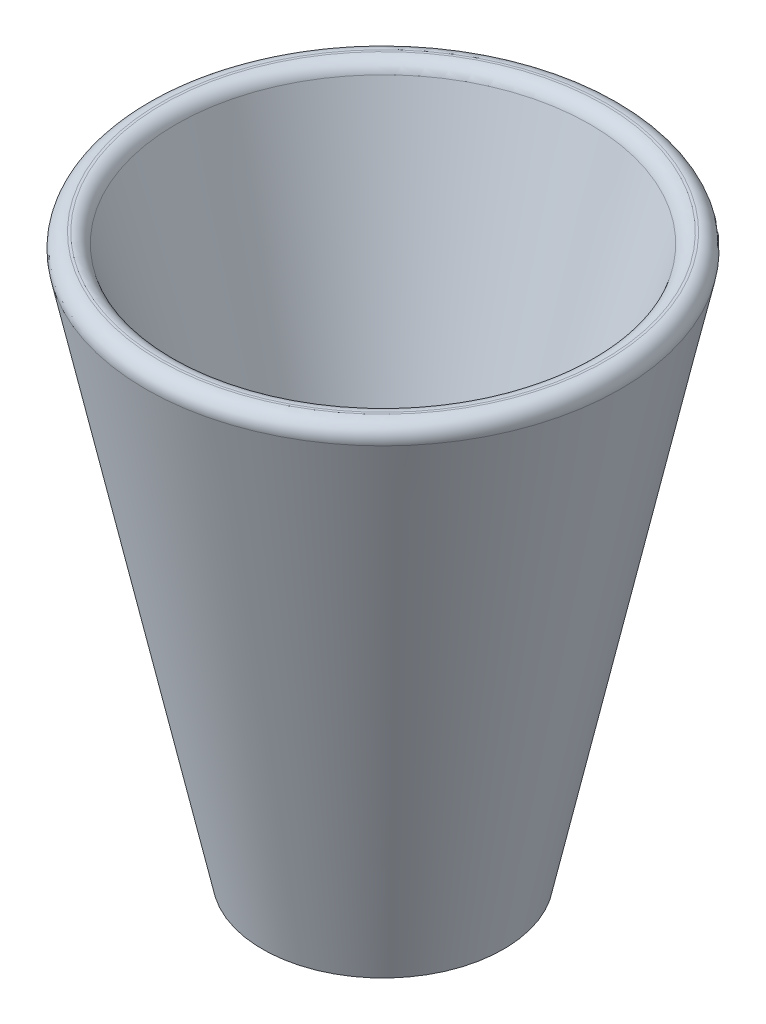
SolidWorks part; units mm, degrees
ref_plane "Front Plane" through (0, 0, 0) normal (0, 0, 1) x (1, 0, 0)
ref_plane "Top Plane" through (0, 0, 0) normal (0, 1, 0) x (1, 0, 0)
ref_plane "Right Plane" through (0, 0, 0) normal (1, 0, 0) x (0, 0, -1)
sketch "Sketch3" plane through (0, 0, 0) normal (0, 0, 1) x (1, 0, 0)
  line L0 (0, 0) -> (12.7, 0)
  line L1 (12.7, 0) -> (25.4, 59.1004)
  line L2 (25.4, 59.1004) -> (22.1403, 59.1004)
  line L3 (22.1403, 59.1004) -> (9.2281, 16.9829)
  line L5 (0, 10.16) -> (0, 0)
  line L6 (0, 0) -> (0, 64.1456) construction
  line L7 (-33.9711, 10.16) -> (34.5135, 10.16) construction
  arc A0 (9.2281, 16.9829) -> (0, 10.16) centre (0, 19.812) cw
  point P9 (31.8336, 9.8733)
  point P10 (0, 0)
  point P11 (0, 0)
  point P12 (0, 0)
  point P13 (0, 0)
  dimension "D4" = 9.652
  dimension "D1" = 25.4
  dimension "D2" = 12.7
  dimension "D3" = 10.16
  dimension "D5" = 3.2597
  dimension "D6" = 10.16
  dimension "D7" = 59.1004
revolve "Revolve1" add sketch "Sketch3" angle 360 about L6
fillet "Fillet1" radius 1.524 2 edges at (0, 59.1004, -25.4) (0, 59.1004, -22.1403)
sketch "Sketch4" plane through (0, 0, 0) normal (0, -1, 0) x (1, 0, 0)
  circle A0 centre (0, 0) radius 8.89
extrude "Cut-Extrude1" cut sketch "Sketch4" against normal blind 5.08
fillet "Fillet2" radius 5.08 1 edges at (0, 5.08, -8.89)
